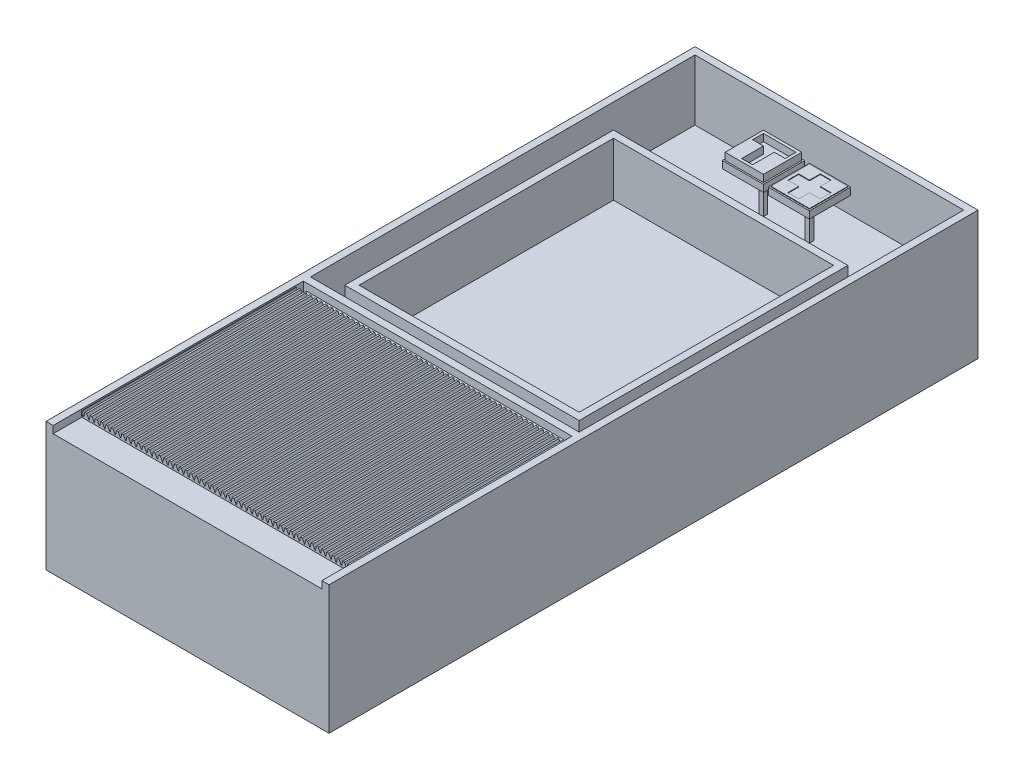
SolidWorks part; units mm, degrees
ref_plane "Front Plane" through (0, 0, 0) normal (0, 0, 1) x (1, 0, 0)
ref_plane "Top Plane" through (0, 0, 0) normal (0, 1, 0) x (1, 0, 0)
ref_plane "Right Plane" through (0, 0, 0) normal (1, 0, 0) x (0, 0, -1)
sketch "Sketch1" plane through (0, 0, 0) normal (0, 1, 0) x (1, 0, 0)
  line L0 (-470, -1035) -> (470, -1035)
  line L1 (-495, -1135) -> (495, -1135)
  line L2 (-495, -1135) -> (-495, 1135)
  line L3 (-495, 1135) -> (495, 1135)
  line L4 (495, -1135) -> (495, 1135)
  line L5 (-495, -1135) -> (495, 1135) construction
  line L6 (-495, 1135) -> (495, -1135) construction
  line L7 (-495, -260) -> (495, -260) construction
  line L8 (-457.5, -260) -> (457.5, -260)
  line L9 (-470, -1135) -> (-470, 1110)
  line L10 (-470, 1110) -> (470, 1110)
  line L11 (470, -1135) -> (470, 1110)
  line L12 (-495, -1135) -> (-470, -1135)
  line L13 (495, -1135) -> (470, -1135)
  line L14 (-457.5, -1035) -> (457.5, -1035)
  line L15 (-457.5, -260) -> (-457.5, -1035)
  line L16 (457.5, -260) -> (457.5, -1035)
  line L17 (-470, -285) -> (470, -285)
  point P0 (0, 0)
  dimension "D3" = 100
  dimension "D4" = 875
  dimension "D5" = 37.5
  dimension "D6" = 37.5
  dimension "D8" = 25
  dimension "D7" = 25
extrude "Boss-Extrude1" add sketch "Sketch1" along normal blind 25 contours L9 L17 L15 L8 L16 L11 L10 | L17 L15 L0 L16 | L15 L17 L16 L8 | L17 L9 L0 L15 | L17 L16 L0 L11 region at (-463.75, 0, 660) region at (0, 0, 660) region at (0, 0, -424.6617) region at (463.75, 0, 660) region at (0, 0, 272.5)
extrude "Boss-Extrude2" add sketch "Sketch1<3>" along normal blind 450 contours L11 L1 L4 L3 L2 L9 L10 region at (-494.7649, 0, 1085)
sketch "Sketch1<3>" plane through (0, 0, 0) normal (0, 1, 0) x (1, 0, 0) same geometry as "Sketch1"
extrude "Boss-Extrude3" add sketch "Sketch1<4>" along normal blind 425 contours L1 L11 L0 L9 region at (0, 0, 1085)
sketch "Sketch1<4>" plane through (0, 0, 0) normal (0, 1, 0) x (1, 0, 0) same geometry as "Sketch1"
extrude "Boss-Extrude4" add sketch "Sketch1<5>" along normal blind 400 from surface contours L17 L9 L0 L15 | L17 L15 L0 L16 | L15 L17 L16 L8 | L17 L16 L0 L11 region at (-463.75, 0, 660) region at (0, 0, 660) region at (463.75, 0, 660) region at (0, 0, 272.5) starting at face at (0, 25, -37.5)
sketch "Sketch1<5>" plane through (0, 0, 0) normal (0, 1, 0) x (1, 0, 0) same geometry as "Sketch1"
sketch "Sketch2" plane through (-495, 0, 0) normal (-1, 0, 0) x (0, 0, 1)
  line L6 (-1110, 237.5) -> (235, 237.5)
  line L7 (235, 237.5) -> (235, 212.5)
  line L8 (235, 212.5) -> (-1110, 212.5)
  line L9 (-1110, 212.5) -> (-1110, 237.5)
  line L10 (260, 25) -> (235, 25)
  line L11 (235, 25) -> (235, 450)
  line L12 (235, 450) -> (260, 450)
  line L13 (260, 450) -> (260, 25)
  line L14 (260, 25) -> (285, 25)
  line L15 (260, 25) -> (285, 25)
  line L16 (285, 425) -> (1135, 425)
  line L17 (285, 425) -> (1135, 425)
  line L19 (-1110, 450) -> (-1110, 25)
  line L20 (1135, 450) -> (-1110, 450)
  line L25 (-1110, 450) -> (-1110, 25) construction
  line L26 (1135, 450) -> (-1110, 450) construction
  line L29 (260, 425) -> (260, 25)
  line L33 (260, 425) -> (260, 25) construction
  line L34 (-1135, 450) -> (-1135, 0) construction
  line L37 (285, 425) -> (260, 425)
  line L38 (285, 425) -> (260, 425)
  line L40 (285, 25) -> (285, 425)
  line L41 (285, 25) -> (285, 425)
  line L48 (-1110, 25) -> (285, 25)
  line L49 (-1110, 25) -> (285, 25)
  line L50 (1135, 425) -> (1135, 450)
  line L51 (1135, 425) -> (1135, 450)
  line L54 (285, 25) -> (285, 425)
  line L55 (285, 25) -> (285, 425)
  point P21 (-1135, 225)
  point P22 (-1110, 225)
  line M18 (1135, 450) -> (-1135, 450)
  dimension "D3" = 25
  dimension "D4" = 25
  dimension "D5" = 25
extrude "Boss-Extrude5" add sketch "Sketch2" against normal up to surface (965 mm away) contours L8 L9 L6 L7 up to face at (470, 300, 103.3333)
extrude "Stone On Counter" add sketch "Sketch2<3>" against normal up to surface (965 mm away) from surface contours L13 L11 L7 L10 M18 region at (-495, 237.5, 247.5) up to face at (470, 270, -113) starting at face at (-470, 270, -113)
sketch "Sketch2<3>" plane through (-495, 0, 0) normal (-1, 0, 0) x (0, 0, 1) same geometry as "Sketch2"
sketch "Sketch3" plane through (0, 237.5, 0) normal (0, 1, 0) x (1, 0, 0)
  line L2 (0, -1135) -> (0, 1135) construction
  line L3 (-495, 1135) -> (495, 1135) construction
  line L16 (470, -235) -> (470, 1110) construction
  line L17 (470, -235) -> (-470, -235) construction
  line L22 (-410, 765) -> (-410, -175)
  line L23 (-410, -175) -> (410, -175)
  line L24 (410, -175) -> (410, 765)
  line L25 (410, 765) -> (-410, 765)
  line L34 (385, 740) -> (-385, 740)
  line L35 (-385, 740) -> (-385, -150)
  line L36 (-385, -150) -> (385, -150)
  line L37 (385, -150) -> (385, 740)
  point P11 (0, 0)
  dimension "D4" = 60
  dimension "D1" = 60
  dimension "D2" = 25
  dimension "D3" = 1000
extrude "Boss-Extrude7" add sketch "Sketch3" along normal offset from surface (187.5 mm away) 25 contours L24 L25 L22 L23 L37 L36 L35 L34 region at (0, 237.5, -752.526) up to face at (0, 450, -437.5)
sketch "Sketch4" plane through (0, 0, 260) normal (0, 0, 1) x (1, 0, 0)
  line L0 (-470, 425) -> (470, 425) construction
  line L1 (-470, 425) -> (470, 425) construction
  line L2 (-470, 425) -> (-470, 445)
  line L6 (-468.3129, 430) -> (-462.1795, 430)
  line L7 (-462.1795, 430) -> (-459.1129, 445)
  line L8 (-459.1129, 445) -> (-452.9795, 445)
  line L9 (-452.9795, 445) -> (-444.9872, 430)
  line L10 (-444.9872, 430) -> (-444.9872, 425)
  line L11 (-444.9872, 425) -> (-470, 425)
  line L12 (-468.3129, 430) -> (-468.3129, 425)
  line L13 (470, 445) -> (460, 445)
  line L14 (460, 445) -> (460, 425)
  line L15 (460, 425) -> (470, 425)
  line L16 (470, 425) -> (470, 445)
  line L18 (470, 450) -> (-470, 450) construction
  line L19 (-470, 445) -> (-468.3129, 445)
  line L20 (-468.3129, 445) -> (-468.3129, 425)
  line M609 (-470, 450) -> (-470, 25)
  line M612 (-457.5, 425) -> (457.5, 425)
  line M615 (470, 25) -> (470, 450)
  dimension "D1" = 5
  dimension "D2" = 6.1333
  dimension "D4" = 6.1333
  dimension "D6" = 3.0667
  dimension "D7" = 10
  dimension "D9" = 5
extrude "Boss-Extrude11" add sketch "Sketch4" along normal offset from surface (750 mm away) 100 from offset 25 contours L20 L19 L11 L12 M609 | L14 L15 L13 M615 region at (-469.1564, 435, 260) region at (465, 435, 260) up to face at (0, 331.25, 1135)
extrude "Boss-Extrude12" add sketch "Sketch4<4>" along normal up to surface (775 mm away) from offset 25 contours L6 L12 L10 L9 L8 L7 M612 region at (-455.4321, 432.7888, 260) up to face at (-469.1564, 435, 1035)
sketch "Sketch4<4>" plane through (0, 0, 260) normal (0, 0, 1) x (1, 0, 0) same geometry as "Sketch4"
pattern_linear "LPattern2" count 50 spacing 18.4 along (1, 0, 0) of "Boss-Extrude12"
sketch "Sketch5" plane through (0, 237.5, 0) normal (0, 1, 0) x (1, 0, 0)
  line L0 (0, 0) -> (0, 1680.9655) construction
  line L1 (-152.5, 1829.3937) -> (-152.5, 375.7778) construction
  line L2 (1047.5, 1554.0652) -> (1047.5, 254.3965) construction
  line L3 (-870.6909, 1035) -> (784.2404, 1035) construction
  line L4 (-495, 1135) -> (495, 1135) construction
  line L5 (-840.0627, 885) -> (814.8685, 885) construction
  line L6 (410, 765) -> (-410, 765) construction
  line L7 (-137.5, 1017) -> (-23.5, 1017)
  line L8 (-152.5, 1032) -> (-8.5, 1032)
  line L9 (-152.5, 1032) -> (-152.5, 888)
  line L10 (-152.5, 888) -> (-8.5, 888)
  line L11 (-8.5, 1032) -> (-8.5, 888)
  line L12 (-80.5, 888) -> (-80.5, 1032) construction
  line L13 (-152.5, 960) -> (-8.5, 960) construction
  line L14 (8.5, 1032) -> (152.5, 1032)
  line L15 (8.5, 1032) -> (8.5, 888)
  line L16 (8.5, 888) -> (152.5, 888)
  line L17 (152.5, 1032) -> (152.5, 888)
  line L18 (80.5, 888) -> (80.5, 1032) construction
  line L19 (8.5, 960) -> (152.5, 960) construction
  line L20 (-23.5, 1017) -> (-23.5, 979)
  line L21 (-23.5, 979) -> (-61.5, 979)
  line L22 (-61.5, 979) -> (-61.5, 903)
  line L23 (-61.5, 903) -> (-99.5, 903)
  line L24 (-99.5, 903) -> (-99.5, 979)
  line L25 (-99.5, 979) -> (-137.5, 979)
  line L26 (-137.5, 979) -> (-137.5, 1017)
  line L27 (-147.5, 1027) -> (-147.5, 893)
  line L28 (-147.5, 893) -> (-13.5, 893)
  line L29 (-13.5, 1027) -> (-13.5, 893)
  line L30 (-147.5, 1027) -> (-13.5, 1027)
  line L31 (13.5, 1027) -> (13.5, 893)
  line L32 (13.5, 893) -> (147.5, 893)
  line L33 (147.5, 1027) -> (147.5, 893)
  line L34 (13.5, 1027) -> (147.5, 1027)
  line L35 (99.5, 1017) -> (61.5, 1017)
  line L36 (61.5, 1017) -> (61.5, 979)
  line L37 (61.5, 979) -> (23.5, 979)
  line L38 (23.5, 979) -> (23.5, 941)
  line L39 (99.5, 1017) -> (99.5, 979)
  line L40 (99.5, 979) -> (137.5, 979)
  line L41 (137.5, 979) -> (137.5, 941)
  line L42 (99.5, 941) -> (137.5, 941)
  line L43 (99.5, 903) -> (99.5, 941)
  line L44 (61.5, 941) -> (23.5, 941)
  line L45 (99.5, 903) -> (61.5, 903)
  line L46 (61.5, 903) -> (61.5, 941)
  line L47 (-470, 1110) -> (-470, -235) construction
  line L48 (-88, 952.5) -> (-73, 952.5)
  line L49 (-88, 952.5) -> (-88, 967.5)
  line L50 (-88, 967.5) -> (-73, 967.5)
  line L51 (-73, 952.5) -> (-73, 967.5)
  line L52 (-88, 952.5) -> (-73, 967.5) construction
  line L53 (-88, 967.5) -> (-73, 952.5) construction
  line L54 (73, 952.5) -> (88, 952.5)
  line L55 (73, 952.5) -> (73, 967.5)
  line L56 (73, 967.5) -> (88, 967.5)
  line L57 (88, 952.5) -> (88, 967.5)
  line L58 (73, 952.5) -> (88, 967.5) construction
  line L59 (73, 967.5) -> (88, 952.5) construction
  point P2 (-80.5, 960)
  point P50 (80.5, 960)
  point P55 (137.5, 960)
  point P59 (23.5, 960)
  point P131 (-80.5, 960)
  point P152 (80.5, 960)
  dimension "D8" = 15
  dimension "D1" = 1200
  dimension "D2" = 317.5
  dimension "D3" = 100
  dimension "D4" = 120
  dimension "D5" = 144
  dimension "D6" = 3
  dimension "D7" = 305
  dimension "D9" = 15
  dimension "D10" = 15
  dimension "D11" = 5
  dimension "D13" = 15
  dimension "D14" = 15
  dimension "D12" = 5
extrude "Boss-Extrude13" add sketch "Sketch5" along normal offset from surface (137.5 mm away) 75 contours L48 L51 L50 L49 | L54 L57 L56 L55 up to face at (0, 450, -437.5)
extrude "Boss-Extrude14" add sketch "Sketch5<3>" along normal blind 25 from surface separate body contours L11 L8 L9 L10 L27 L30 L29 L28 | L30 L27 L28 L29 L25 L26 L7 L20 L21 L22 L23 L24 | L26 L25 L24 L23 L22 L21 L20 L7 | L17 L14 L15 L16 L31 L34 L33 L32 | L34 L31 L32 L33 L45 L46 L44 L38 L37 L36 L35 L39 L40 L41 L42 L43 | L46 L45 L43 L42 L41 L40 L39 L35 L36 L37 L38 L44 | L48 L51 L50 L49 | L54 L57 L56 L55 region at (-80.5, 237.5, -975.6889) region at (-80.5, 237.5, -1029.9635) region at (80.5, 237.5, -1029.9635) region at (-80.5, 237.5, -1025.105) region at (80.5, 237.5, -1025.105) region at (97.8878, 237.5, -998) region at (-80.5, 237.5, -960) region at (80.5, 237.5, -960) starting at face at (80.5, 375, -960)
sketch "Sketch5<3>" plane through (0, 237.5, 0) normal (0, 1, 0) x (1, 0, 0) same geometry as "Sketch5"
extrude "Boss-Extrude15" add sketch "Sketch5<4>" along normal blind 2 from surface contours L34 L31 L32 L33 L45 L46 L44 L38 L37 L36 L35 L39 L40 L41 L42 L43 region at (80.5, 237.5, -1025.105) starting at face at (-80.5, 400, -960)
sketch "Sketch5<4>" plane through (0, 237.5, 0) normal (0, 1, 0) x (1, 0, 0) same geometry as "Sketch5"
extrude "Boss-Extrude17" add sketch "Sketch5<5>" along normal blind 25 from surface contours L30 L27 L28 L29 L25 L26 L7 L20 L21 L22 L23 L24 region at (-80.5, 237.5, -1025.105) starting at face at (-80.5, 400, -960)
sketch "Sketch5<5>" plane through (0, 237.5, 0) normal (0, 1, 0) x (1, 0, 0) same geometry as "Sketch5"
equation "\"Length\"= 990"
equation "\"Height\"= 2270"
equation "\"Thick\"= 450"
equation "\"S\"=25"
equation "\"D2@Sketch1\"=\"Length\""
equation "\"D1@Sketch1\"=\"Height\""
equation "\"D5@Sketch1\"=\"S\"*1.5"
equation "\"D6@Sketch1\"=\"S\"*1.5"
equation "\"D4@Sketch1\"=900-\"S\""
equation "\"D7@Sketch1\"=\"S\""
equation "\"D1@Boss-Extrude1\"=\"S\""
equation "\"D1@Boss-Extrude2\"=\"Thick\""
equation "\"D1@Boss-Extrude3\"=\"Thick\"-\"S\""
equation "\"D1@Boss-Extrude4\"=\"Thick\"-2*\"S\""
equation "\"D3@Sketch2\"=\"S\""
equation "\"D4@Sketch2\"=\"S\""
equation "\"A\"=60"
equation "\"D1@Boss-Extrude7\"=\"S\""
equation "\"RibbonLength\"= 920"
equation "\"RibbonNum\"= 50"
equation "\"RibbonRecWid\"= ( \"Length\" - 2 * \"S\" - \"RibbonLength\" ) / 2"
equation "\"RibbonTrapWid\"= \"RibbonLength\" / \"RibbonNum\""
equation "\"D2@Sketch4\"=\"RibbonTrapWid\"/3"
equation "\"D6@Sketch4\"=\"RibbonTrapWid\"/6"
equation "\"D4@Sketch4\"=\"RibbonTrapWid\"/3"
equation "\"D8@Sketch1\"=\"S\""
equation "\"D19@Boss-Extrude11\"=\"S\""
equation "\"D19@Boss-Extrude12\"=\"S\""
equation "\"D3@LPattern2\"=\"RibbonTrapWid\""
equation "\"D1@LPattern2\"=\"RibbonNum\""
equation "\"D5@Sketch2\"=\"S\""
equation "\"D4@Sketch3\"=\"A\""
equation "\"D1@Boss-Extrude13\"=3*\"S\""
equation "\"D1@Sketch3\"=\"A\""
equation "\"D2@Sketch3\"=\"S\""
equation "\"D7@Sketch4\"=\"RibbonRecWid\""
